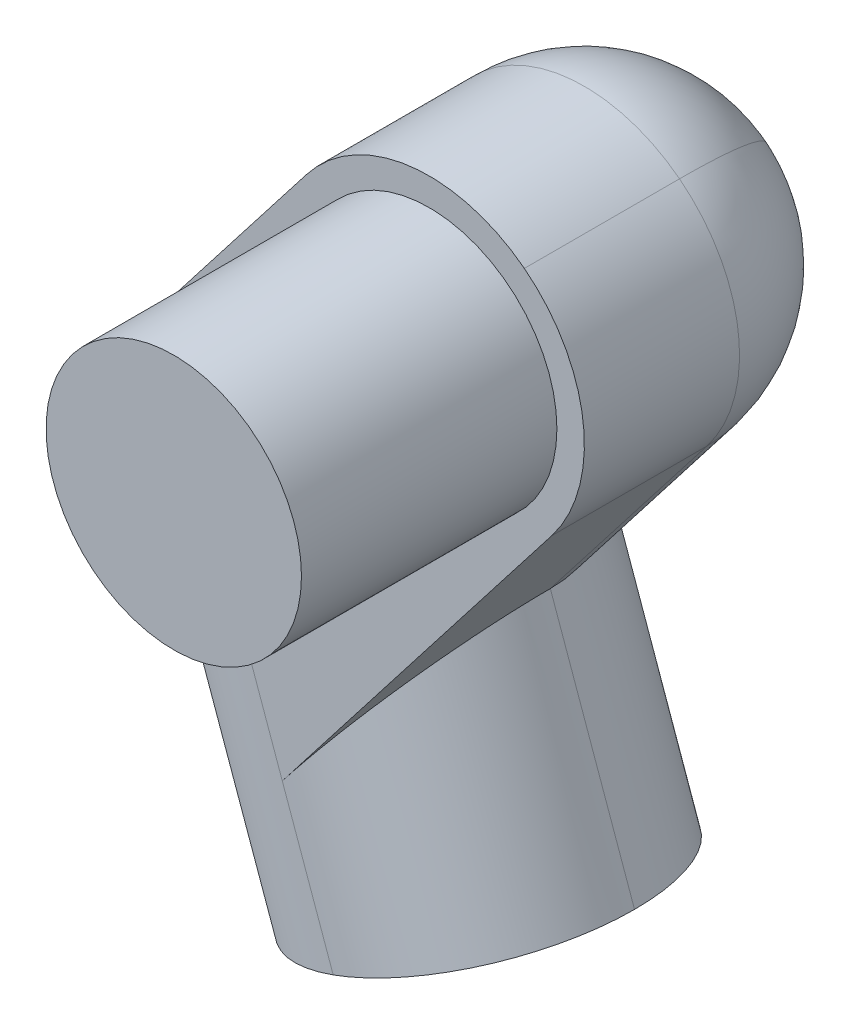
SolidWorks part; units mm, degrees
ref_plane "Front Plane" through (0, 0, 0) normal (0, 0, 1) x (1, 0, 0)
ref_plane "Top Plane" through (0, 0, 0) normal (0, 1, 0) x (1, 0, 0)
ref_plane "Right Plane" through (0, 0, 0) normal (1, 0, 0) x (0, 0, -1)
sketch "Sketch1" plane through (0, 0, 0) normal (0, 0, 1) x (1, 0, 0)
  line L1 (38.8847, 109.2543) -> (-61.2604, -19.7614) construction
  line L2 (-61.2604, -19.7614) -> (-27.772, -113.5288) construction
  line L4 (-61.2604, -19.7614) -> (38.8847, 109.2543)
  line L6 (38.8847, 109.2543) -> (-58.6295, 184.9471)
  line L7 (-58.6295, 184.9471) -> (-200.2781, 2.4629)
  line L8 (-61.2604, -19.7614) -> (-27.772, -113.5288)
  line L9 (-27.772, -113.5288) -> (-144.0244, -155.0475)
  line L10 (-144.0244, -155.0475) -> (-200.2781, 2.4629)
  dimension "D1" = 99.568
  dimension "D2" = 123.444
  dimension "D3" = 123.444
  dimension "D4" = 163.322
extrude "Boss-Extrude1" add sketch "Sketch1" along normal blind 123.444
fillet "Fillet1" radius 61.722 6 edges at (-129.4538, 93.705, 0) (-172.1513, -76.2923, 0) (-44.5162, -66.6451, 0) (-11.1879, 44.7464, 0) (-172.1513, -76.2923, 123.444) (-44.5162, -66.6451, 123.444)
fillet "Fillet2" radius 61.722 4 edges at (38.8847, 109.2543, 92.583) (-58.6295, 184.9471, 92.583) (-44.3489, 173.8621, 18.078) (24.604, 120.3392, 18.078)
sketch "Sketch2" plane through (0, 0, 123.444) normal (0, 0, 1) x (1, 0, 0)
  line L0 (-96.4759, 136.19) -> (-155.3907, 60.2908) construction
  circle A0 centre (-47.7188, 98.3436) radius 50.8
  dimension "D1" = 101.6
  dimension "D2" = 61.722
  dimension "D3" = 61.722
extrude "Boss-Extrude2" add sketch "Sketch2" along normal blind 101.6
sketch "Sketch3" plane through (32.8177, -91.8896, 0) normal (0.3363, -0.9417, 0) x (-0.9417, -0.3363, 0)
  circle A0 centre (126.0599, -61.722) radius 50.8
  dimension "D1" = 101.6
  dimension "D2" = 61.722
  dimension "D3" = 61.722
extrude "Cut-Extrude1" cut sketch "Sketch3" against normal blind 101.6
